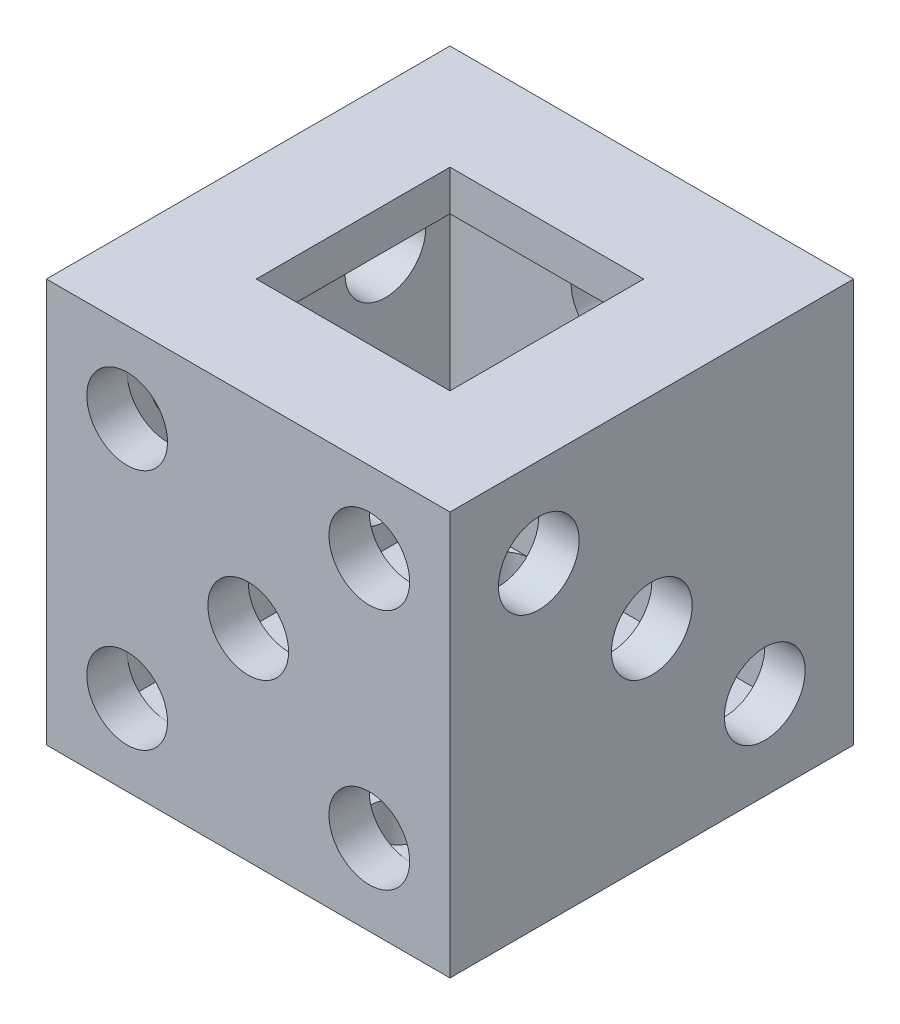
SolidWorks part; units mm, degrees
ref_plane "Front Plane" through (0, 0, 0) normal (0, 0, 1) x (1, 0, 0)
ref_plane "Top Plane" through (0, 0, 0) normal (0, 1, 0) x (1, 0, 0)
ref_plane "Right Plane" through (0, 0, 0) normal (1, 0, 0) x (0, 0, -1)
sketch "Sketch1" plane through (0, 0, 0) normal (0, 1, 0) x (1, 0, 0)
  line L1 (-12.5, 12.5) -> (12.5, 12.5)
  line L2 (-12.5, 12.5) -> (-12.5, -12.5)
  line L3 (-12.5, -12.5) -> (12.5, -12.5)
  line L4 (12.5, 12.5) -> (12.5, -12.5)
  line L5 (0, -12.5) -> (0, 12.5) construction
  line L6 (-12.5, 0) -> (12.5, 0) construction
  point P0 (0, 0)
  dimension "D1" = 25
  dimension "D2" = 25
extrude "Boss-Extrude1" add sketch "Sketch1" along normal blind 25
shell "Shell1" thickness 2.5
sketch "Sketch2" plane through (0, 25, 0) normal (0, 1, 0) x (1, 0, 0)
  line L1 (-6, 6) -> (6, 6)
  line L2 (-6, 6) -> (-6, -6)
  line L3 (-6, -6) -> (6, -6)
  line L4 (6, 6) -> (6, -6)
  line L5 (0, -6) -> (0, 6) construction
  line L6 (-6, 0) -> (6, 0) construction
  point P0 (0, 0)
  dimension "D1" = 12
  dimension "D2" = 12
extrude "Cut-Extrude1" cut sketch "Sketch2" against normal blind 15
sketch "Sketch3" plane through (0, 0, 0) normal (0, -1, 0) x (1, 0, 0)
  line L1 (10, 10) -> (-10, 10) construction
  line L2 (10, 10) -> (10, -10) construction
  line L3 (10, -10) -> (-10, -10) construction
  line L4 (-10, 10) -> (-10, -10) construction
  line L5 (0, -10) -> (0, 10) construction
  line L6 (10, 0) -> (-10, 0) construction
  line L7 (5, -8.25) -> (-5, -8.25) construction
  line L8 (5, -8.25) -> (5, 8.25) construction
  line L9 (5, 8.25) -> (-5, 8.25) construction
  line L10 (-5, -8.25) -> (-5, 8.25) construction
  line L11 (0, 8.25) -> (0, -8.25) construction
  line L12 (5, 0) -> (-5, 0) construction
  circle A0 centre (-5, 8.25) radius 1.75
  circle A1 centre (-5, 0) radius 1.75
  circle A2 centre (-5, -8.25) radius 1.75
  circle A3 centre (5, 8.25) radius 1.75
  circle A4 centre (5, 0) radius 1.75
  circle A5 centre (5, -8.25) radius 1.75
  point P0 (0, 0)
  point P4 (0, 0)
  dimension "D5" = 3.5
  dimension "D6" = 3.5
  dimension "D7" = 3.5
  dimension "D8" = 3.5
  dimension "D9" = 3.5
  dimension "D10" = 3.5
  dimension "D1" = 20
  dimension "D2" = 20
  dimension "D3" = 10
  dimension "D4" = 16.5
extrude "Cut-Extrude2" cut sketch "Sketch3" against normal blind 15
sketch "Sketch4" plane through (12.5, 0, 0) normal (1, 0, 0) x (0, 0, -1)
  line L0 (7, 5.5) -> (12.5, 5.5) construction
  line L1 (12.5, 25) -> (12.5, 0) construction
  line L4 (-12.5, 0) -> (12.5, 0)
  line L5 (12.5, 0) -> (12.5, 25)
  line L6 (12.5, 25) -> (-12.5, 25)
  line L7 (-12.5, 25) -> (-12.5, 0)
  line L8 (-12.5, 0) -> (12.5, 0)
  line L10 (12.5, 25) -> (-12.5, 25)
  line L11 (-12.5, 25) -> (-12.5, 0)
  line L13 (7, 5.5) -> (7, 0) construction
  line L14 (-7, 19.5) -> (-7, 25) construction
  line L15 (-7, 19.5) -> (-12.5, 19.5) construction
  circle A0 centre (-7, 19.5) radius 2.5
  circle A1 centre (0, 12.5) radius 2.5
  circle A2 centre (7, 5.5) radius 2.5
  dimension "D5" = 5
  dimension "D6" = 5
  dimension "D7" = 5
  dimension "D8" = 5.5
  dimension "D2" = 5.5
  dimension "D3" = 5.5
  dimension "D4" = 5.5
  dimension "D1" = 0
extrude "Cut-Extrude6" cut sketch "Sketch4" against normal blind 15 contours A0
extrude "Cut-Extrude7" cut sketch "Sketch4<3>" against normal blind 15 contours A1 | A2 region at (12.5, 12.5, 0) region at (12.5, 5.5, -7)
sketch "Sketch4<3>" plane through (12.5, 0, 0) normal (1, 0, 0) x (0, 0, -1) same geometry as "Sketch4"
sketch "Sketch5" plane through (-12.5, 0, 0) normal (-1, 0, 0) x (0, 0, 1)
  line L0 (-12.5, 12.5) -> (0, 12.5) construction
  line L2 (-10, 22.5) -> (10, 22.5) construction
  line L3 (-10, 22.5) -> (-10, 2.5) construction
  line L4 (-12.5, 0) -> (12.5, 0)
  line L5 (12.5, 0) -> (12.5, 25)
  line L6 (12.5, 25) -> (-12.5, 25)
  line L7 (-12.5, 25) -> (-12.5, 0)
  line L8 (-12.5, 0) -> (12.5, 0)
  line L9 (12.5, 0) -> (12.5, 25)
  line L10 (12.5, 25) -> (-12.5, 25)
  line L11 (-12.5, 25) -> (-12.5, 0)
  line L12 (-10, 2.5) -> (10, 2.5) construction
  line L13 (10, 22.5) -> (10, 2.5) construction
  line L14 (0, 2.5) -> (0, 22.5) construction
  line L15 (-10, 12.5) -> (10, 12.5) construction
  line L16 (-6, 18.5) -> (6, 18.5) construction
  line L17 (-6, 18.5) -> (-6, 6.5) construction
  line L18 (-6, 6.5) -> (6, 6.5) construction
  line L19 (6, 18.5) -> (6, 6.5) construction
  line L20 (0, 6.5) -> (0, 18.5) construction
  line L21 (-6, 12.5) -> (6, 12.5) construction
  circle A0 centre (-6, 18.5) radius 2.5
  circle A1 centre (6, 18.5) radius 2.5
  circle A2 centre (6, 6.5) radius 2.5
  circle A3 centre (-6, 6.5) radius 2.5
  dimension "D6" = 5
  dimension "D7" = 5
  dimension "D8" = 5
  dimension "D9" = 5
  dimension "D2" = 20
  dimension "D3" = 20
  dimension "D4" = 12
  dimension "D5" = 12
  dimension "D1" = 0
extrude "Cut-Extrude8" cut sketch "Sketch5" against normal blind 15 contours A0
extrude "Cut-Extrude9" cut sketch "Sketch5<4>" against normal blind 15 contours A1
sketch "Sketch5<4>" plane through (-12.5, 0, 0) normal (-1, 0, 0) x (0, 0, 1) same geometry as "Sketch5"
extrude "Cut-Extrude10" cut sketch "Sketch5<5>" against normal blind 15 contours A3 | A2
sketch "Sketch5<5>" plane through (-12.5, 0, 0) normal (-1, 0, 0) x (0, 0, 1) same geometry as "Sketch5"
sketch "Sketch7" plane through (0, 0, 12.5) normal (0, 0, 1) x (1, 0, 0)
  line L0 (0, 25) -> (0, 12.5) construction
  line L2 (-10, 22.5) -> (10, 22.5) construction
  line L3 (-10, 22.5) -> (-10, 2.5) construction
  line L4 (-12.5, 0) -> (12.5, 0)
  line L5 (12.5, 0) -> (12.5, 25)
  line L6 (12.5, 25) -> (-12.5, 25)
  line L7 (-12.5, 25) -> (-12.5, 0)
  line L8 (-12.5, 0) -> (12.5, 0)
  line L9 (12.5, 0) -> (12.5, 25)
  line L10 (12.5, 25) -> (-12.5, 25)
  line L11 (-12.5, 25) -> (-12.5, 0)
  line L12 (-10, 2.5) -> (10, 2.5) construction
  line L13 (10, 22.5) -> (10, 2.5) construction
  line L14 (0, 2.5) -> (0, 22.5) construction
  line L15 (-10, 12.5) -> (10, 12.5) construction
  line L16 (-7.5, 20) -> (7.5, 20) construction
  line L17 (-7.5, 20) -> (-7.5, 5) construction
  line L18 (-7.5, 5) -> (7.5, 5) construction
  line L19 (7.5, 20) -> (7.5, 5) construction
  line L20 (0, 5) -> (0, 20) construction
  line L21 (-7.5, 12.5) -> (7.5, 12.5) construction
  circle A0 centre (-7.5, 20) radius 2.5
  circle A1 centre (0, 12.5) radius 2.5
  circle A2 centre (7.5, 20) radius 2.5
  circle A3 centre (7.5, 5) radius 2.5
  circle A4 centre (-7.5, 5) radius 2.5
  dimension "D7" = 5
  dimension "D8" = 5
  dimension "D9" = 5
  dimension "D10" = 5
  dimension "D11" = 5
  dimension "D2" = 12.5
  dimension "D3" = 20
  dimension "D4" = 20
  dimension "D5" = 15
  dimension "D6" = 15
  dimension "D1" = 0
extrude "Cut-Extrude11" cut sketch "Sketch7" against normal blind 15 contours A1 | A2 | A0 | A4 | A3
sketch "Sketch8" plane through (0, 0, -12.5) normal (0, 0, -1) x (-1, 0, 0)
  line L0 (0, 0) -> (0, 12.5) construction
  line L1 (10, 22.5) -> (-10, 2.5) construction
  line L2 (-10, 22.5) -> (10, 22.5) construction
  line L3 (-10, 22.5) -> (-10, 2.5) construction
  line L4 (-12.5, 0) -> (12.5, 0)
  line L5 (12.5, 0) -> (12.5, 25)
  line L6 (12.5, 25) -> (-12.5, 25)
  line L7 (-12.5, 25) -> (-12.5, 0)
  line L8 (-12.5, 0) -> (12.5, 0)
  line L9 (12.5, 0) -> (12.5, 25)
  line L10 (12.5, 25) -> (-12.5, 25)
  line L11 (-12.5, 25) -> (-12.5, 0)
  line L12 (-10, 2.5) -> (10, 2.5) construction
  line L13 (10, 22.5) -> (10, 2.5) construction
  line L14 (0, 2.5) -> (0, 22.5) construction
  line L15 (-10, 12.5) -> (10, 12.5) construction
  line L17 (-6, 18.5) -> (6, 18.5) construction
  line L18 (-6, 18.5) -> (-6, 6.5) construction
  line L19 (-6, 6.5) -> (6, 6.5) construction
  line L20 (6, 18.5) -> (6, 6.5) construction
  line L21 (0, 6.5) -> (0, 18.5) construction
  line L22 (-6, 12.5) -> (6, 12.5) construction
  circle A2 centre (0, 18.5) radius 2.5
  circle A3 centre (0, 6.5) radius 2.5
  dimension "D7" = 5
  dimension "D8" = 5
  dimension "D2" = 12.5
  dimension "D3" = 20
  dimension "D4" = 20
  dimension "D5" = 12
  dimension "D6" = 12
  dimension "D1" = 0
extrude "Cut-Extrude12" cut sketch "Sketch8" against normal blind 10 contours A2 | A3
